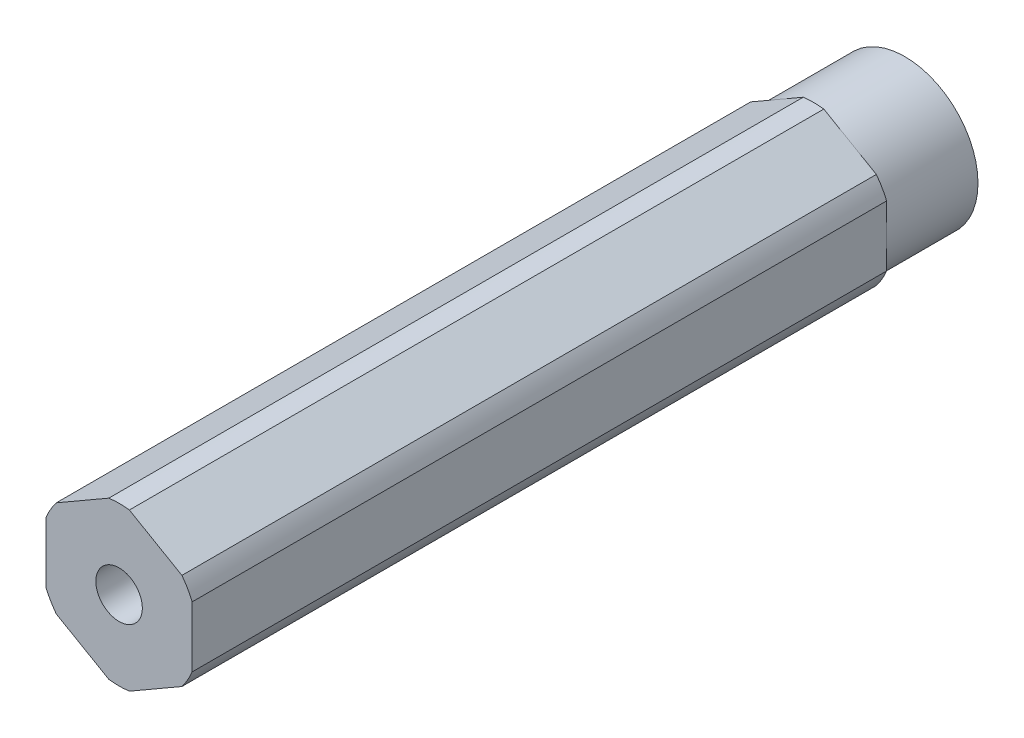
SolidWorks part; units mm, degrees
material "6061-T6 (SS)"
ref_plane "Front Plane" through (0, 0, 0) normal (0, 0, 1) x (1, 0, 0)
ref_plane "Top Plane" through (0, 0, 0) normal (0, 1, 0) x (1, 0, 0)
ref_plane "Right Plane" through (0, 0, 0) normal (1, 0, 0) x (0, 0, -1)
sketch "Sketch1" plane through (0, 0, 0) normal (0, 0, 1) x (1, 0, 0)
  line L0 (0, 7.3323) -> (-0.893, 6.8168) construction
  line L1 (-0.893, 6.8168) -> (-5.457, 4.1818)
  line L2 (-6.35, 2.635) -> (-6.35, -2.635)
  line L3 (-5.457, -4.1818) -> (-0.893, -6.8168)
  line L4 (0.893, -6.8168) -> (5.457, -4.1818)
  line L5 (6.35, -2.635) -> (6.35, 2.635)
  line L6 (5.457, 4.1818) -> (0.893, 6.8168)
  line L7 (0.893, 6.8168) -> (0, 7.3323) construction
  circle A0 centre (0, 0) radius 6.35 construction
  arc A2 (-6.35, -2.635) -> (-5.457, -4.1818) centre (0, 0) ccw
  arc A3 (-5.457, 4.1818) -> (-6.35, 2.635) centre (0, 0) ccw
  arc A4 (0.893, 6.8168) -> (-0.893, 6.8168) centre (0, 0) ccw
  arc A5 (-0.893, -6.8168) -> (0.893, -6.8168) centre (0, 0) ccw
  arc A6 (5.457, -4.1818) -> (6.35, -2.635) centre (0, 0) ccw
  arc A7 (6.35, 2.635) -> (5.457, 4.1818) centre (0, 0) ccw
  dimension "D1" = 12.7
  dimension "D2" = 13.75
extrude "Boss-Extrude1" add sketch "Sketch1" along normal mid plane 68.2625
sketch "Sketch3" plane through (0, 0, 34.1313) normal (0, 0, 1) x (1, 0, 0)
  circle A0 centre (0, 0) radius 2.0193
  dimension "D1" = 4.0386
extrude "Cut-Extrude1" cut sketch "Sketch3" against normal through all
sketch "Sketch8" plane through (0, 0, -34.1313) normal (0, 0, -1) x (-1, 0, 0)
  circle A0 centre (0, 0) radius 6.35
  circle A1 centre (0, 0) radius 6.875
  arc A2 (0.893, 6.8168) -> (-0.893, 6.8168) centre (0, 0) ccw construction
  dimension "D1" = 12.7
extrude "Cut-Extrude3" cut sketch "Sketch8" against normal blind 7.9375
